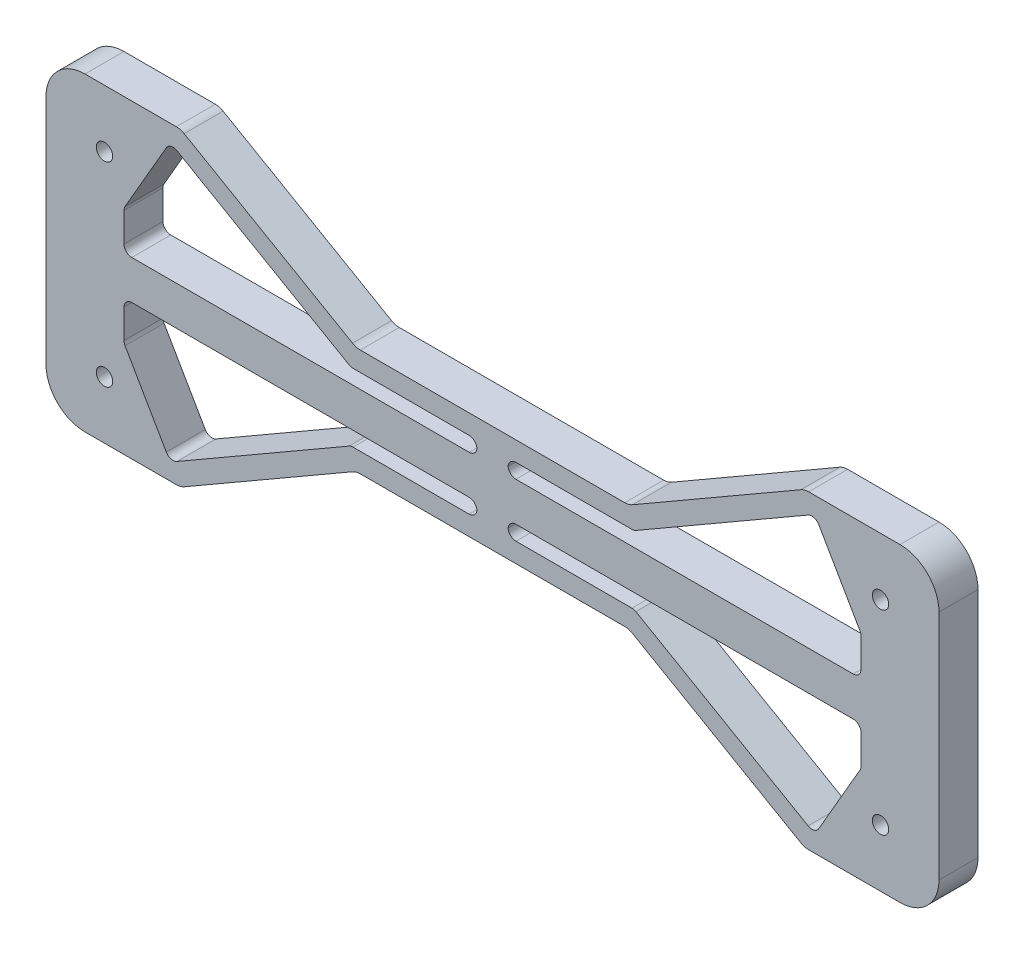
SolidWorks part; units mm, degrees
ref_plane "前视基准面" through (0, 0, 0) normal (0, 0, 1) x (1, 0, 0)
ref_plane "上视基准面" through (0, 0, 0) normal (0, 1, 0) x (1, 0, 0)
ref_plane "右视基准面" through (0, 0, 0) normal (1, 0, 0) x (0, 0, -1)
other "Configuration Table"
sketch "草图1" plane through (0, 0, 0) normal (0, 0, 1) x (1, 0, 0)
  line L1 (-114.5, 39.75) -> (114.5, 39.75)
  line L2 (-114.5, 39.75) -> (-114.5, -39.75)
  line L3 (-114.5, -39.75) -> (114.5, -39.75)
  line L4 (114.5, 39.75) -> (114.5, -39.75)
  line L5 (-114.5, 39.75) -> (114.5, -39.75) construction
  line L6 (-114.5, -39.75) -> (114.5, 39.75) construction
  point P0 (0, 0)
  dimension "D1" = 229
  dimension "D2" = 79.5
extrude "凸台-拉伸1" add sketch "草图1" along normal blind 10
fillet "圆角1" radius 10 4 edges at (114.5, -39.75, 5) (114.5, 39.75, 5) (-114.5, -39.75, 5) (-114.5, 39.75, 5)
sketch "草图2" plane through (0, 0, 0) normal (0, 0, -1) x (-1, 0, 0)
  line L0 (0, 0) -> (95.0941, 0) construction
  line L1 (114.5, 29.75) -> (114.5, -29.75) construction
  line L2 (0, 0) -> (0, 105.0009) construction
  circle A0 centre (99.5, 25) radius 2.1
  circle A1 centre (99.5, -25) radius 2.1
  circle A2 centre (-99.5, -25) radius 2.1
  circle A3 centre (-99.5, 25) radius 2.1
  dimension "D1" = 4.2
  dimension "D2" = 50
  dimension "D3" = 15
extrude "切除-拉伸1" cut sketch "草图2" against normal through all
sketch "草图3" plane through (0, 0, 0) normal (0, 0, -1) x (-1, 0, 0)
  line L1 (-97.3927, 21.35) -> (-95.2853, 25)
  line L2 (-95.2853, 25) -> (-97.3927, 28.65)
  line L3 (-97.3927, 28.65) -> (-101.6073, 28.65)
  line L4 (-101.6073, 28.65) -> (-103.7147, 25)
  line L5 (-103.7147, 25) -> (-101.6073, 21.35)
  line L6 (-101.6073, 21.35) -> (-97.3927, 21.35)
  line L7 (-97.3927, -28.65) -> (-95.2853, -25)
  line L8 (-95.2853, -25) -> (-97.3927, -21.35)
  line L9 (-97.3927, -21.35) -> (-101.6073, -21.35)
  line L10 (-101.6073, -21.35) -> (-103.7147, -25)
  line L11 (-103.7147, -25) -> (-101.6073, -28.65)
  line L12 (-101.6073, -28.65) -> (-97.3927, -28.65)
  line L13 (101.6073, 21.35) -> (103.7147, 25)
  line L14 (103.7147, 25) -> (101.6073, 28.65)
  line L15 (101.6073, 28.65) -> (97.3927, 28.65)
  line L16 (97.3927, 28.65) -> (95.2853, 25)
  line L17 (95.2853, 25) -> (97.3927, 21.35)
  line L18 (97.3927, 21.35) -> (101.6073, 21.35)
  line L19 (101.6073, -28.65) -> (103.7147, -25)
  line L20 (103.7147, -25) -> (101.6073, -21.35)
  line L21 (101.6073, -21.35) -> (97.3927, -21.35)
  line L22 (97.3927, -21.35) -> (95.2853, -25)
  line L23 (95.2853, -25) -> (97.3927, -28.65)
  line L24 (97.3927, -28.65) -> (101.6073, -28.65)
  circle A1 centre (-99.5, 25) radius 3.65 construction
  circle A2 centre (-99.5, -25) radius 3.65 construction
  circle A3 centre (99.5, 25) radius 3.65 construction
  circle A4 centre (99.5, -25) radius 3.65 construction
  dimension "D1" = 7.3
extrude "切除-拉伸2" cut sketch "草图3" against normal blind 4.5
sketch "草图4" plane through (0, 0, 0) normal (0, 0, -1) x (-1, 0, 0)
  line L0 (-80, 39.75) -> (-34.9667, 13.75)
  line L1 (-104.5, 39.75) -> (104.5, 39.75) construction
  line L2 (-34.9667, 13.75) -> (34.9667, 13.75)
  line L3 (0, 13.75) -> (0, 39.75) construction
  line L4 (-80, 39.75) -> (80, 39.75)
  line L5 (80, 39.75) -> (34.9667, 13.75)
  line L6 (0, 0) -> (69.5264, 0) construction
  line L7 (0, -13.75) -> (0, -39.75) construction
  line L8 (80, -39.75) -> (34.9667, -13.75)
  line L9 (-80, -39.75) -> (80, -39.75)
  line L10 (-34.9667, -13.75) -> (34.9667, -13.75)
  line L11 (-80, -39.75) -> (-34.9667, -13.75)
  dimension "D1" = 26
  dimension "D2" = 30
  dimension "D3" = 80
extrude "切除-拉伸3" cut sketch "草图4" against normal through all
fillet "圆角2" radius 4 8 edges at (34.9667, 13.75, 5) (80, 39.75, 5) (80, -39.75, 5) (34.9667, -13.75, 5) (-34.9667, -13.75, 5) (-80, -39.75, 5) (-80, 39.75, 5) (-34.9667, 13.75, 5)
sketch "草图6" plane through (0, 0, 0) normal (0, 0, -1) x (-1, 0, 0)
  line L0 (-82.6579, 35.5111) -> (-94.5, 15)
  line L1 (-94.5, 15) -> (-94.5, 5)
  line L2 (-94.5, 5) -> (-4, 5)
  line L3 (-4, 5) -> (-4, 8.75)
  line L4 (-4, 8.75) -> (-36.3064, 8.75)
  line L5 (-36.3064, 8.75) -> (-82.6579, 35.5111)
  line L6 (0, 0) -> (-135.1586, 0) construction
  line L7 (-33.8949, 13.75) -> (33.8949, 13.75) construction
  line L8 (-79.0718, 39.2141) -> (-35.8949, 14.2859) construction
  line L9 (-114.5, -29.75) -> (-114.5, 29.75) construction
  line L10 (0, 0) -> (0, 41.0144) construction
  line L11 (36.3064, 8.75) -> (82.6579, 35.5111)
  line L12 (4, 8.75) -> (36.3064, 8.75)
  line L13 (4, 5) -> (4, 8.75)
  line L14 (94.5, 5) -> (4, 5)
  line L15 (94.5, 15) -> (94.5, 5)
  line L16 (82.6579, 35.5111) -> (94.5, 15)
  line L17 (82.6579, -35.5111) -> (94.5, -15)
  line L18 (94.5, -15) -> (94.5, -5)
  line L19 (94.5, -5) -> (4, -5)
  line L20 (4, -5) -> (4, -8.75)
  line L21 (4, -8.75) -> (36.3064, -8.75)
  line L22 (36.3064, -8.75) -> (82.6579, -35.5111)
  line L23 (-36.3064, -8.75) -> (-82.6579, -35.5111)
  line L24 (-4, -8.75) -> (-36.3064, -8.75)
  line L25 (-4, -5) -> (-4, -8.75)
  line L26 (-94.5, -5) -> (-4, -5)
  line L27 (-94.5, -15) -> (-94.5, -5)
  line L28 (-82.6579, -35.5111) -> (-94.5, -15)
  dimension "D1" = 10
  dimension "D2" = 5
  dimension "D3" = 5
  dimension "D4" = 20
  dimension "D5" = 10
  dimension "D6" = 8
extrude "切除-拉伸4" cut sketch "草图6" against normal through all
fillet "圆角3" radius 2 24 edges at (36.3064, 8.75, 5) (4, 8.75, 5) (94.5, 5, 5) (94.5, 15, 5) (82.6579, 35.5111, 5) (4, 5, 5) (-36.3064, 8.75, 5) (-82.6579, 35.5111, 5) (-94.5, 15, 5) (-4, 5, 5) (-4, 8.75, 5) (-94.5, 5, 5) (36.3064, -8.75, 5) (82.6579, -35.5111, 5) (94.5, -15, 5) (94.5, -5, 5) (4, -5, 5) (4, -8.75, 5) (-36.3064, -8.75, 5) (-4, -8.75, 5) (-4, -5, 5) (-94.5, -5, 5) (-94.5, -15, 5) (-82.6579, -35.5111, 5)
